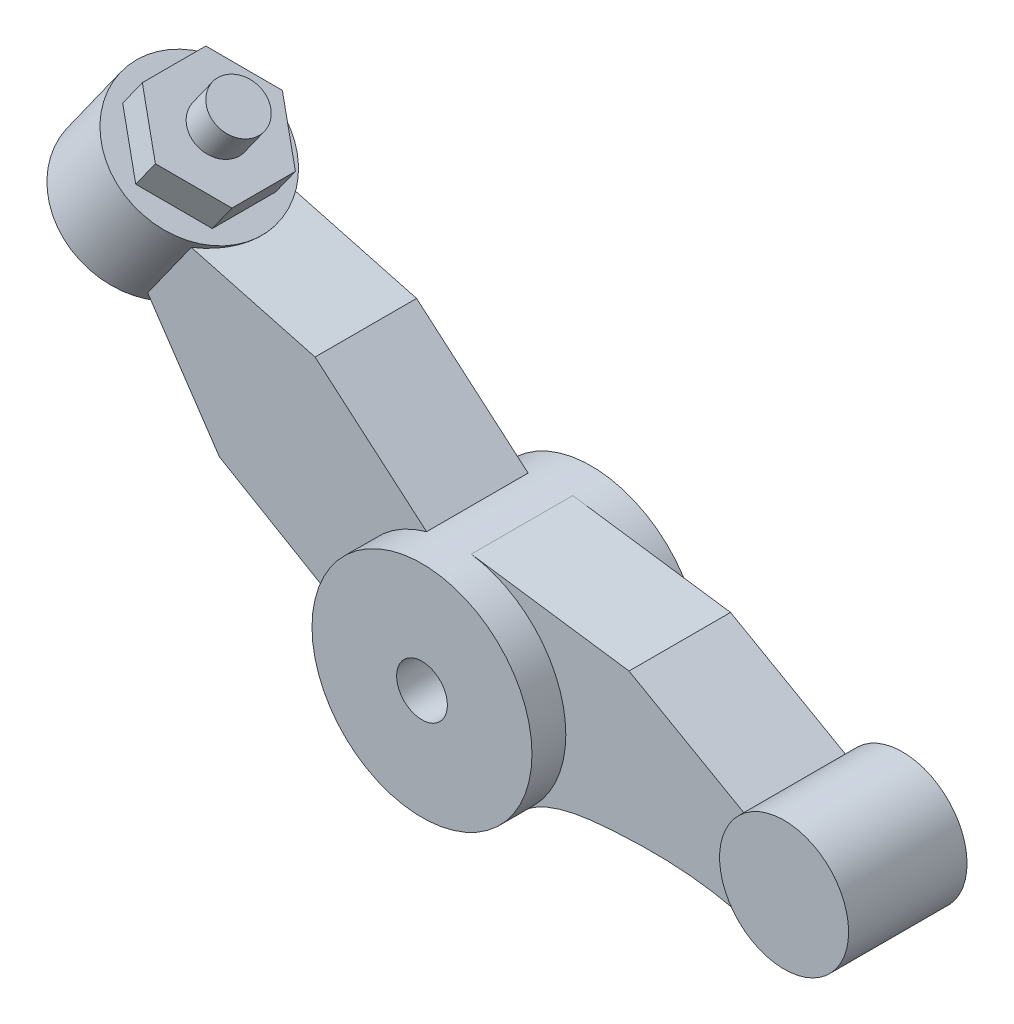
SolidWorks part; units mm, degrees
ref_plane "Front Plane" through (0, 0, 0) normal (0, 0, 1) x (1, 0, 0)
ref_plane "Top Plane" through (0, 0, 0) normal (0, 1, 0) x (1, 0, 0)
ref_plane "Right Plane" through (0, 0, 0) normal (1, 0, 0) x (0, 0, -1)
sketch "Sketch1" plane through (0, 0, 0) normal (0, 0, 1) x (1, 0, 0)
  line L0 (-52.1384, 0) -> (84.9739, 0) construction
  line L1 (0, 0) -> (0, 38.7811) construction
  line L2 (0, 0) -> (-91.847, 65.4413) construction
  line L3 (86.4956, 6.3824) -> (51.9954, 25.9908)
  line L4 (51.9954, 25.9908) -> (4.6268, 32.6942)
  line L5 (-86.8725, 72.4229) -> (-96.8214, 58.4597)
  line L6 (-86.8725, 72.4229) -> (-42.2626, 60.5021)
  line L7 (-42.2626, 60.5021) -> (-8.7815, 31.8309)
  line L8 (-70.9864, 20.1882) -> (-32.9535, -2.0946)
  line L9 (-96.8214, 58.4597) -> (-70.9864, 20.1882)
  circle A0 centre (0, 0) radius 33.02
  circle A1 centre (0, 0) radius 7.62
  circle A2 centre (101.092, -6.3473) radius 19.3675
  spline S0 degree 3 poles (89.317, -21.7241) (75.2765, -17.4262) (52.8366, -16.671) (28.0082, -19.7897) (20.8199, -25.6291) knots 0 0 0 0 0.609502 1 1 1 1
  dimension "D1" = 15.24
  dimension "D2" = 66.04
  dimension "D3" = 38.735
  dimension "D4" = 17.3228
  dimension "D5" = 101.092
  dimension "D6" = 112.776
  dimension "D7" = 17.145
  dimension "D8" = 20.828
  dimension "D9" = 35.47
extrude "Boss-Extrude1" add sketch "Sketch1" along normal mid plane 50.8 contours A0 A1 region at (24.2257, 21.0388, 0)
extrude "Boss-Extrude2" add sketch "Sketch1<3>" along normal mid plane 35.56 separate body contours A2 region at (101.092, -6.3473, 0)
sketch "Sketch1<3>" plane through (0, 0, 0) normal (0, 0, 1) x (1, 0, 0) same geometry as "Sketch1"
extrude "Boss-Extrude3" add sketch "Sketch1<4>" along normal mid plane 30.48 contours S0 A2 L3 L4 A0 region at (53.1563, 2.9957, 0)
sketch "Sketch1<4>" plane through (0, 0, 0) normal (0, 0, 1) x (1, 0, 0) same geometry as "Sketch1"
extrude "Boss-Extrude4" add sketch "Sketch1<5>" along normal mid plane 30.48 contours A0 L7 L6 L5 L9 L8 region at (-54.6249, 38.9205, 0)
sketch "Sketch1<5>" plane through (0, 0, 0) normal (0, 0, 1) x (1, 0, 0) same geometry as "Sketch1"
sketch "Sketch5" plane through (0, 0, 0) normal (0, 0, 1) x (1, 0, 0)
  line L0 (-96.8214, 58.4597) -> (-86.2093, 73.3538)
  line L1 (-86.2093, 73.3538) -> (-94.4838, 79.2494)
  line L2 (-94.4838, 79.2494) -> (-122.6039, 39.7827)
  line L3 (-109.2999, 50.5845) -> (-96.8214, 58.4597)
  line L4 (-86.8725, 72.4229) -> (-96.8214, 58.4597) construction
  arc A0 (-122.6039, 39.7827) -> (-109.2999, 50.5845) centre (-117.4453, 47.0229) ccw
  dimension "D3" = 8.89
  dimension "D1" = 18.288
  dimension "D2" = 10.16
  dimension "D4" = 25.4
revolve "Revolve2" add sketch "Sketch5" angle 360 about L2
sketch "Sketch6" plane through (0, 0, 0) normal (0, 0, 1) x (1, 0, 0)
  line L0 (-94.4838, 79.2494) -> (-118.8166, 45.0983) construction
  line L1 (-86.2093, 73.3538) -> (-102.7583, 85.145) construction
  line L2 (-108.1934, 60.0079) -> (-92.2753, 82.3491)
  line L3 (-92.2753, 82.3491) -> (-111.0997, 95.7616)
  line L4 (-111.0997, 95.7616) -> (-127.0179, 73.4204)
  line L5 (-127.0179, 73.4204) -> (-108.1934, 60.0079)
  dimension "D1" = 27.432
  dimension "D2" = 23.114
revolve "Revolve4" add sketch "Sketch6" angle 360 about L0
sketch "Sketch7" plane through (7.8462, 11.0122, 0) normal (0.5803, 0.8144, 0) x (0.8144, -0.5803, 0)
  line L1 (-106.426, -9.5321) -> (-106.426, 9.5321)
  line L2 (-106.426, 9.5321) -> (-122.936, 19.0641)
  line L3 (-122.936, 19.0641) -> (-139.446, 9.5321)
  line L4 (-139.446, 9.5321) -> (-139.446, -9.5321)
  line L5 (-139.446, -9.5321) -> (-122.936, -19.0641)
  line L6 (-122.936, -19.0641) -> (-106.426, -9.5321)
  circle A0 centre (-122.936, 0) radius 16.51 construction
  dimension "D1" = 33.02
extrude "Boss-Extrude5" add sketch "Sketch7" along normal blind 10.16
sketch "Sketch8" plane through (13.7418, 19.2867, 0) normal (0.5803, 0.8144, 0) x (0.8144, -0.5803, 0)
  circle A0 centre (-122.936, 0) radius 7.62
  dimension "D1" = 15.24
extrude "Boss-Extrude6" add sketch "Sketch8" along normal blind 10.16
